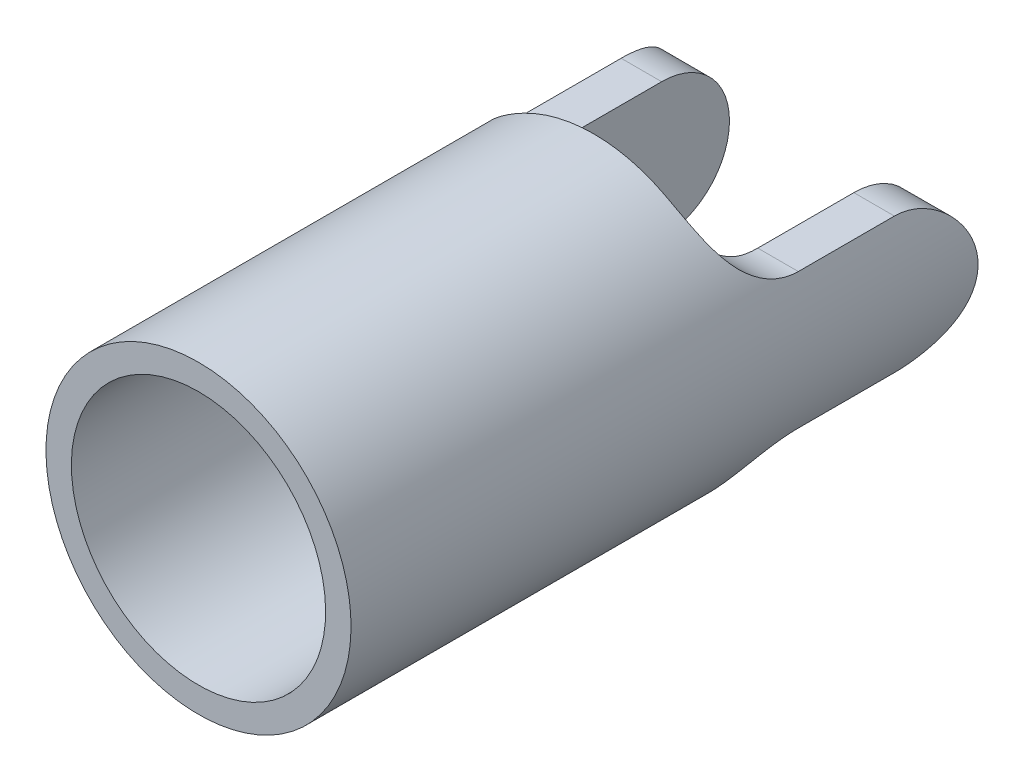
SolidWorks part; units mm, degrees
material "AISI 1020"
ref_plane "Front Plane" through (0, 0, 0) normal (0, 0, 1) x (1, 0, 0)
ref_plane "Top Plane" through (0, 0, 0) normal (0, 1, 0) x (1, 0, 0)
ref_plane "Right Plane" through (0, 0, 0) normal (1, 0, 0) x (0, 0, -1)
sketch "Sketch1" plane through (0, 0, 0) normal (1, 0, 0) x (0, 0, -1)
  line L0 (0, 0) -> (-34.925, 0) construction
  line L1 (-34.925, 9.525) -> (-34.925, 7.9375)
  line L2 (-34.925, 7.9375) -> (-15.925, 7.9375)
  line L3 (-15.925, 7.9375) -> (-15.925, 0)
  line L4 (-15.925, 0) -> (9.525, 0)
  line L5 (-34.925, 9.525) -> (9.525, 9.525)
  line L6 (9.525, 9.525) -> (9.525, 0)
  arc A0 (0, 9.525) -> (9.525, 0) centre (0, 0) cw construction
  dimension "D3" = 15.875
  dimension "D1" = 34.925
  dimension "D2" = 19
  dimension "D4" = 19.05
revolve "Revolve1" add sketch "Sketch1" angle 360 about L0
sketch "Sketch3" plane through (0, 0, 0) normal (1, 0, 0) x (0, 0, -1)
  line L0 (9.525, 9.525) -> (-34.925, 9.525) construction
  line L1 (9.525, 9.525) -> (-10.2333, 9.525)
  line L2 (-34.925, -9.525) -> (9.525, -9.525) construction
  line L3 (-10.2333, -9.525) -> (9.525, -9.525)
  line L4 (9.525, -9.525) -> (9.525, 9.525) construction
  line L5 (9.525, -9.525) -> (9.525, 9.525)
  line L6 (-10.2333, 8.4667) -> (-10.2333, 9.525)
  line L7 (-10.2333, -8.4667) -> (-10.2333, -9.525)
  line L8 (0, 4.2333) -> (-6, 4.2333)
  line L9 (0, -4.2333) -> (-6, -4.2333)
  arc A0 (0, -4.2333) -> (0, 4.2333) centre (0, 0) ccw
  arc A1 (-10.2333, 8.4667) -> (-6, 4.2333) centre (-6, 8.4667) ccw
  arc A2 (-10.2333, -8.4667) -> (-6, -4.2333) centre (-6, -8.4667) cw
  dimension "D1" = 4.2333
  dimension "D2" = 4.2333
  dimension "D3" = 6
extrude "Cut-Extrude1" cut sketch "Sketch3" against normal through all and the other way through all
sketch "Sketch4" plane through (0, 0, 0) normal (0, 1, 0) x (1, 0, 0)
  line L0 (-4.3636, -10.2333) -> (4.3636, -10.2333) construction
  line L1 (-2.825, -10.2333) -> (2.825, -10.2333)
  line L2 (0, 0) -> (0, -10.2333) construction
  line L4 (-6, -7.0583) -> (-6, 4.2333)
  line L5 (9.525, 4.2333) -> (-9.525, 4.2333) construction
  line L6 (6, 4.2333) -> (6, -7.0583)
  line L7 (6, 4.2333) -> (-6, 4.2333)
  arc A0 (-6, -7.0583) -> (-2.825, -10.2333) centre (-2.825, -7.0583) ccw
  arc A1 (6, -7.0583) -> (2.825, -10.2333) centre (2.825, -7.0583) cw
  point P14 (-6, -10.2333)
  point P17 (6, -10.2333)
  dimension "D2" = 3.175
  dimension "D1" = 12
extrude "Cut-Extrude2" cut sketch "Sketch4" against normal through all and the other way through all
sketch3d "3DSketch1"
  line L0 (0, 0, 0) -> (0, 0, 34.925)
  line L1 (0, 0, 34.925) -> (0, 0, 10.2333) construction
  line L2 (0, 0, 34.925) -> (0, 0, 15.925) construction
ref_axis "Axis1" through (39.0367, 0, 0) along (-1, 0, 0)
